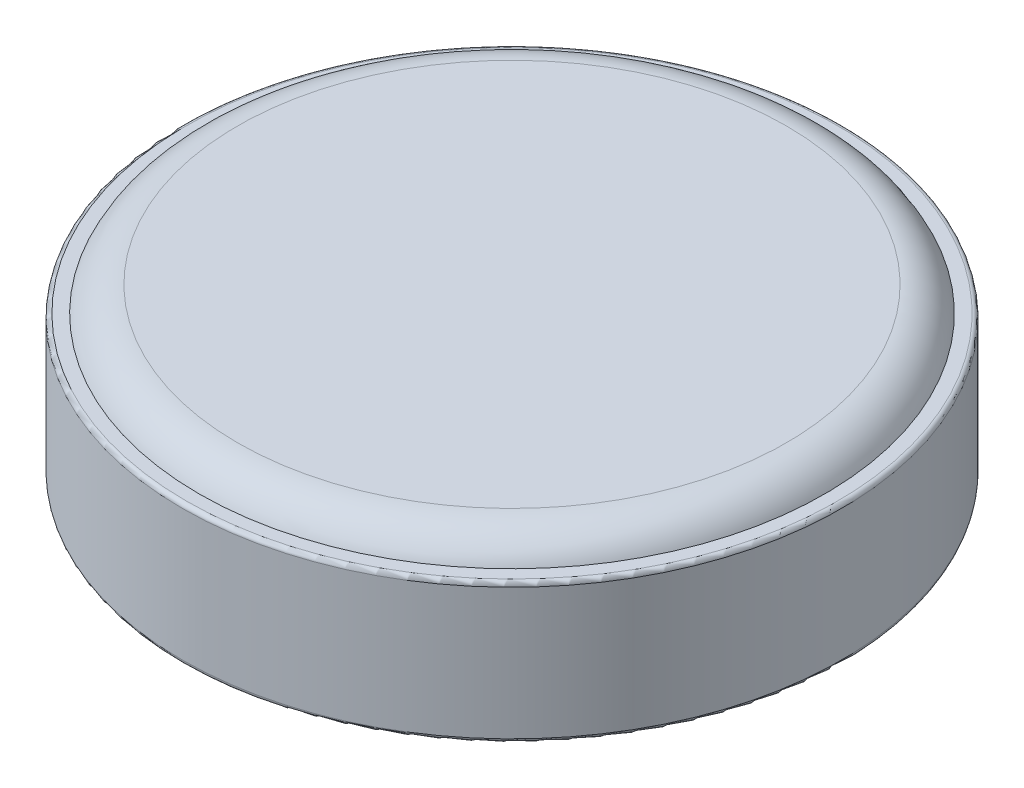
SolidWorks part; units mm, degrees
ref_plane "Front Plane" through (0, 0, 0) normal (0, 0, 1) x (1, 0, 0)
ref_plane "Top Plane" through (0, 0, 0) normal (0, 1, 0) x (1, 0, 0)
ref_plane "Right Plane" through (0, 0, 0) normal (1, 0, 0) x (0, 0, -1)
sketch "Sketch1" plane through (0, 0, 0) normal (0, 1, 0) x (1, 0, 0)
  circle A0 centre (0, 0) radius 10
  dimension "D1" = 20
extrude "Boss-Extrude1" add sketch "Sketch1" along normal blind 5
sketch "Sketch2" plane through (0, 5, 0) normal (0, 1, 0) x (1, 0, 0)
  circle A0 centre (0, 0) radius 10
  circle A1 centre (0, 0) radius 9.492
  circle A2 centre (0, 0) radius 10 construction
  dimension "D1" = 0.508
  dimension "D2" = 0
extrude "Cut-Extrude1" cut sketch "Sketch2" against normal blind 0.762
fillet "Fillet3" radius 1.27 1 edges at (0, 5, 9.492)
fillet "Fillet2" radius 0.127 2 edges at (0, 0, 10) (0, 4.238, 10)
